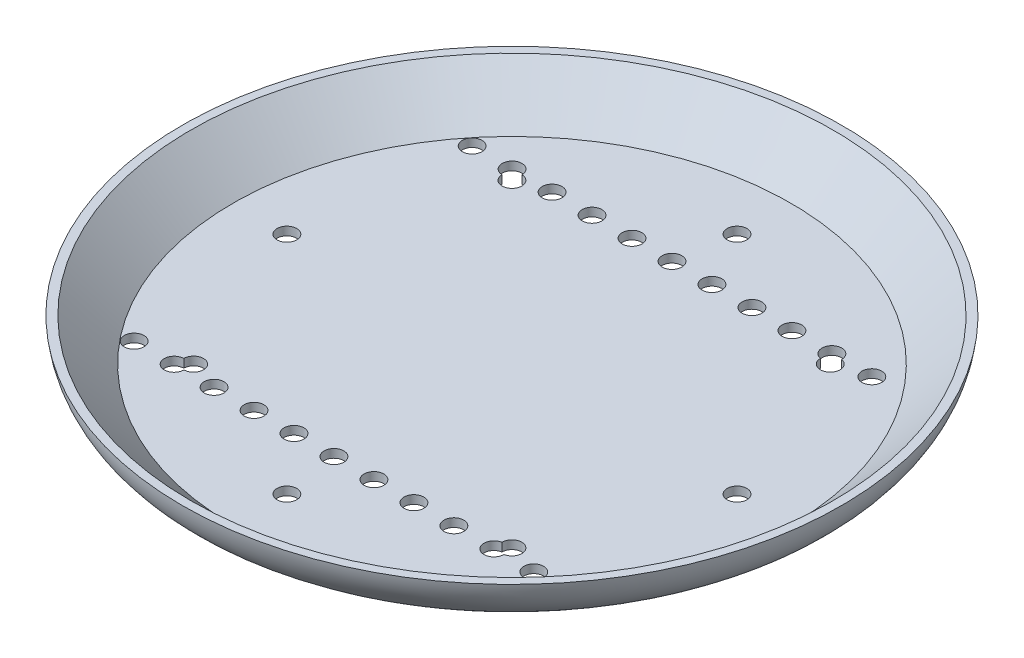
SolidWorks part; units mm, degrees
ref_plane "Front Plane" through (0, 0, 0) normal (0, 0, 1) x (1, 0, 0)
ref_plane "Top Plane" through (0, 0, 0) normal (0, 1, 0) x (1, 0, 0)
ref_plane "Right Plane" through (0, 0, 0) normal (1, 0, 0) x (0, 0, -1)
sketch "Sketch1" plane through (0, 0, 0) normal (0, 1, 0) x (1, 0, 0)
  circle A0 centre (0, 0) radius 58.5
  dimension "D1" = 117
extrude "Boss-Extrude1" add sketch "Sketch1" along normal blind 9
sketch "Sketch2" plane through (0, 9, 0) normal (0, 1, 0) x (1, 0, 0)
  circle A0 centre (0, 0) radius 48.5
  circle A1 centre (0, 0) radius 58.5 construction
  dimension "D1" = 10
extrude "Cut-Extrude1" cut sketch "Sketch2" against normal blind 7.5
chamfer "Chamfer1" distance 8.5 angle 45 1 edges at (0, 9, 48.5)
sketch "Sketch3" plane through (0, 1.5, 0) normal (0, 1, 0) x (1, 0, 0)
  line L0 (-39.3732, 30) -> (39.3732, 30) construction
  line L1 (-39.3732, -30) -> (39.3732, -30) construction
  line L2 (1.9567, 46.9711) -> (1.9567, -13.2336) construction
  line L3 (-55.4067, 0) -> (61.27, 0)
  circle A0 centre (-8.6858, 30) radius 1.75
  circle A1 centre (0, 0) radius 49.5 construction
  circle A2 centre (-37.0658, 30) radius 1.75
  circle A3 centre (-29.9708, 30) radius 1.75
  circle A4 centre (-22.8758, 30) radius 1.75
  circle A5 centre (-15.7808, 30) radius 1.75
  circle A6 centre (-1.5908, 30) radius 1.75
  circle A7 centre (5.5042, 30) radius 1.75
  circle A8 centre (12.5992, 30) radius 1.75
  circle A9 centre (19.6942, 30) radius 1.75
  circle A10 centre (26.7892, 30) radius 1.75
  circle A11 centre (33.8842, 30) radius 1.75
  circle A12 centre (33.8842, -30) radius 1.75
  circle A13 centre (26.7892, -30) radius 1.75
  circle A14 centre (19.6942, -30) radius 1.75
  circle A15 centre (12.5992, -30) radius 1.75
  circle A16 centre (5.5042, -30) radius 1.75
  circle A17 centre (-1.5908, -30) radius 1.75
  circle A18 centre (-15.7808, -30) radius 1.75
  circle A19 centre (-22.8758, -30) radius 1.75
  circle A20 centre (-29.9708, -30) radius 1.75
  circle A21 centre (-37.0658, -30) radius 1.75
  circle A22 centre (-8.6858, -30) radius 1.75
  dimension "D3" = 3.5
  dimension "D4" = 3.5
  dimension "D5" = 3.5
  dimension "D6" = 3.5
  dimension "D10" = 3.5
  dimension "D11" = 3.5
  dimension "D1" = 30
  dimension "D2" = 30
  dimension "D7" = 7.095
  dimension "D8" = 7.095
  dimension "D9" = 7.095
  dimension "D12" = 7.095
  dimension "D13" = 7.095
  dimension "D14" = 3.5475
extrude "Cut-Extrude2" cut sketch "Sketch3" against normal blind 90 contours A21 | A20 | A19 | A18 | A22 | A17 | A16 | A15 | A14 | A13 | A12 | A11 | A10 | A9 | A8 | A7 | A6 | A0 | A5 | A4 | A3 | A2
fillet "Fillet1" radius 10 1 edges at (0, 0, 58.5)
sketch "Sketch5" plane through (0, 1.5, 0) normal (0, 1, 0) x (1, 0, 0)
  line L0 (0, 39.95) -> (0, 0) construction
  circle A0 centre (0, 39.95) radius 1.75
  circle A4 centre (28.2489, 28.2489) radius 1.75
  circle A5 centre (39.95, 0) radius 1.75
  circle A6 centre (28.2489, -28.2489) radius 1.75
  circle A7 centre (0, -39.95) radius 1.75
  circle A8 centre (-28.2489, -28.2489) radius 1.75
  circle A9 centre (-39.95, 0) radius 1.75
  circle A10 centre (-28.2489, 28.2489) radius 1.75
  point P13 (0, 0)
  point P22 (0, 0)
  dimension "D1" = 3.5
  dimension "D2" = 39.95
  dimension "D3" = 8
extrude "Cut-Extrude3" cut sketch "Sketch5" against normal through all
